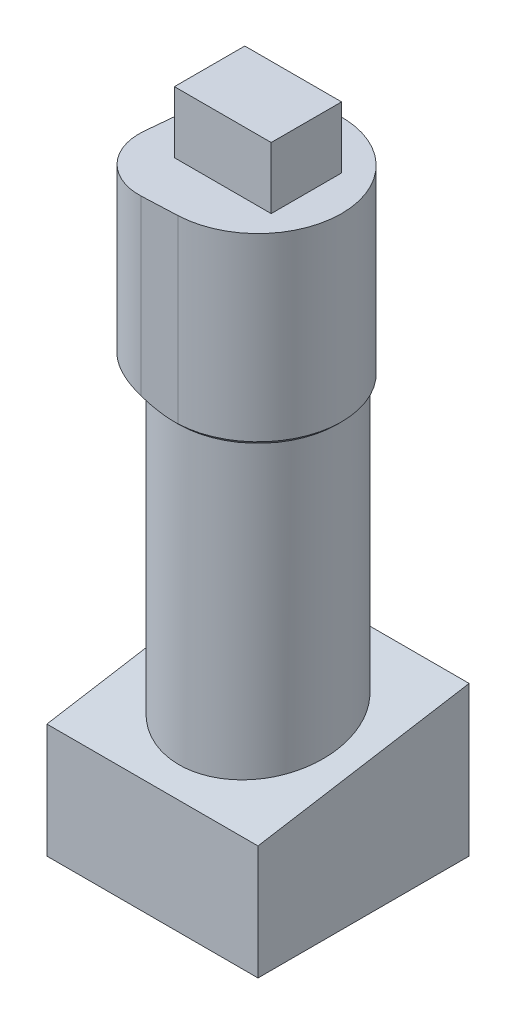
SolidWorks part; units mm, degrees
ref_plane "Front" through (0, 0, 0) normal (0, 0, 1) x (1, 0, 0)
ref_plane "Top" through (0, 0, 0) normal (0, 1, 0) x (1, 0, 0)
ref_plane "Right" through (0, 0, 0) normal (1, 0, 0) x (0, 0, -1)
sketch "Sketch1" plane through (0, 0, 0) normal (0, 1, 0) x (1, 0, 0)
  line L1 (-12, -12) -> (12, -12)
  line L2 (-12, -12) -> (-12, 12)
  line L3 (-12, 12) -> (12, 12)
  line L4 (12, -12) -> (12, 12)
  line L5 (-12, -12) -> (12, 12) construction
  line L6 (-12, 12) -> (12, -12) construction
  point P0 (0, 0)
  dimension "D1" = 24
extrude "Boss-Extrude1" add sketch "Sketch1" along normal blind 17
sketch "Sketch2" plane through (-12, 0, 0) normal (-1, 0, 0) x (0, 0, 1)
  line L0 (-12, 17) -> (12, 13)
  line L1 (12, 17) -> (12, 0) construction
  line L2 (12, 13) -> (12, 17)
  line L3 (12, 17) -> (-12, 17)
  dimension "D1" = 4
extrude "Cut-Extrude1" cut sketch "Sketch2" against normal through all
sketch "Sketch3" plane through (0, 0, 0) normal (0, -1, 0) x (1, 0, 0)
  circle A0 centre (0, 0) radius 9
  dimension "D1" = 18
extrude "Boss-Extrude2" add sketch "Sketch3" against normal blind 52
sketch "Sketch4" plane through (0, 52, 0) normal (0, 1, 0) x (1, 0, 0)
  line L0 (-9.4566, 0.9073) -> (-9.8408, -3.0977)
  line L1 (-3.6088, -9.6651) -> (0.4108, -9.4911)
  arc A0 (0.4108, -9.4911) -> (-9.4566, 0.9073) centre (0, 0) ccw
  arc A1 (-9.8408, -3.0977) -> (-3.6088, -9.6651) centre (-3.8683, -3.6707) ccw
  point P1 (0, 0)
  point P3 (-2.1974, -2.6158)
  point P6 (-2.0602, -2.4795)
  point P10 (-4.8141, -5.1274)
  point P11 (-6.0787, -5.7682)
  dimension "D1" = 9.5
  dimension "D2" = 6
extrude "Boss-Extrude3" add sketch "Sketch4" along normal blind 16
chamfer "Chamfer1" distance 5 angle 45 1 edges at (0, 52, -9)
sketch "Sketch5" plane through (0, 68, 0) normal (0, 1, 0) x (1, 0, 0)
  line L5 (-5.5, -4) -> (5.5, -4)
  line L6 (-5.5, -4) -> (-5.5, 4)
  line L7 (-5.5, 4) -> (5.5, 4)
  line L8 (5.5, -4) -> (5.5, 4)
  line L9 (-5.5, -4) -> (5.5, 4) construction
  line L10 (-5.5, 4) -> (5.5, -4) construction
  point P0 (0, 0)
  dimension "D1" = 8
  dimension "D2" = 11
extrude "Boss-Extrude4" add sketch "Sketch5" along normal blind 7
sketch "Sketch6" plane through (0, 0, -12) normal (0, 0, -1) x (-1, 0, 0)
  line L0 (-12, 17) -> (12, 17) construction
  circle A0 centre (5, 12) radius 2.05
  circle A2 centre (-5, 12) radius 2.05
  point P2 (0, 0)
  dimension "D1" = 4.1
  dimension "D2" = 4.1
  dimension "D3" = 5
  dimension "D4" = 5
  dimension "D5" = 5
extrude "Cut-Extrude2" cut sketch "Sketch6" against normal blind 6
